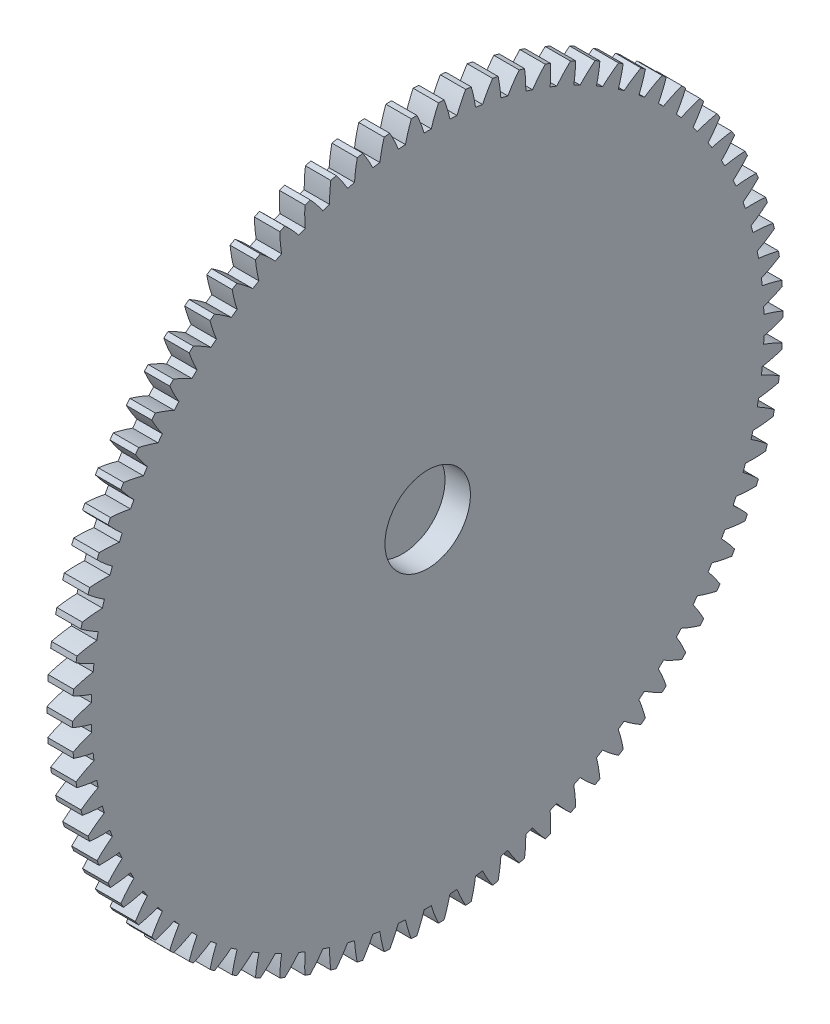
SolidWorks part; units mm, degrees
ref_plane "Plane1" through (0, 0, 0) normal (0, 0, 1) x (1, 0, 0)
ref_plane "Plane2" through (0, 0, 0) normal (0, 1, 0) x (1, 0, 0)
ref_plane "Plane3" through (0, 0, 0) normal (1, 0, 0) x (0, 0, -1)
sketch "HoldingSke" plane through (0, 0, 0) normal (0, 1, 0) x (1, 0, 0)
  line L0 (0, 0) -> (0.1392, -0.9903)
  line L1 (-15, 0) -> (100, 0) construction
  line L2 (0, 0) -> (-2.1039, 2.3779)
  line L3 (0, 0) -> (-11.863, 4.5341)
  line L4 (0, 0) -> (1.2019, 8.552)
  line L5 (0, 0) -> (-46.8476, -17.4728)
  line L6 (0, 0) -> (-2.4869, -1.6779)
  line L7 (-2.1039, 2.3779) -> (8.6586, 51.2059)
  line L8 (-76.2, 54.61) -> (-75.2, 54.61)
  line L9 (-71.009, 38.7566) -> (-53.1078, 45.2721)
  line L10 (-76.2, 71.12) -> (104.1128, 71.12)
  line L11 (0, 0) -> (-3, 0)
  line L12 (-76.2, 101.6) -> (-76.162, 101.6)
  line L13 (24.9733, 27.94) -> (52.9518, 28.4284)
  line L14 (24.9733, 27.94) -> (24.9743, 27.94)
  line L15 (24.9733, 27.94) -> (100.4006, 29.5858)
  line L16 (-63.627, -1) -> (-12.827, -1)
  circle A0 centre (0, 0) radius 3
  circle A1 centre (0, 0) radius 37.5
  circle A2 centre (0, 0) radius 37.5
  circle A3 centre (0, 0) radius 3
  dimension "MHD" = 75
  dimension "Hub_dia" = 75
  dimension "Bore" = 6
  dimension "MBD" = 6
  dimension "Num_teeth" = 82
  dimension "Pitch" = 1
  dimension "Overall_len" = 50
  dimension "Show_teeth" = 82
  dimension "Thickness" = 3
  dimension "OAL" = 50.0001
  dimension "T_dim" = 1
  dimension "Ap" = 20
  dimension "H" = 19.05
  dimension "Pitch_radius" = 180.3128
  dimension "Width" = 3
  dimension "Backlash" = 0.038
  dimension "Addendum_fac" = 1
  dimension "Dedendum_fac" = 1.25
  dimension "Clearance_fac" = 0.25
  dimension "Dedendum_add" = 0.001
  dimension "Module" = 1
sketch "BasProSke" plane through (0, 0, 0) normal (0, 1, 0) x (1, 0, 0)
  line L0 (-10, 0) -> (60, 0) construction
  line L1 (0, 0) -> (0, 42)
  line L2 (0, 0) -> (3, 0)
  line L3 (3, 0) -> (3, 42)
  line L4 (3, 42) -> (0, 42)
  dimension "Thickness" = 3
  dimension "Diameter" = 84
revolve "Base-Revolve" add sketch "BasProSke" angle 360 about L0
sketch "TooCutSke" plane through (0, 0, 0) normal (1, 0, 0) x (0, 0, -1)
  line L1 (0, 0) -> (0, 107) construction
  line L2 (0, 0) -> (-0.8518, 40.9911) construction
  line L3 (0, 0) -> (-3.1403, 81.9272) construction
  line L4 (-0.8518, 40.9911) -> (-1.5702, 40.9636) construction
  arc A0 (0.4198, 39.7468) -> (-0.4198, 39.7468) centre (0, 0) ccw
  arc A1 (1.2904, 42.0056) -> (-1.2904, 42.0056) centre (0, 0) ccw
  circle A2 centre (0, 0) radius 41 construction
  circle A3 centre (0, 0) radius 38.5274 construction
  arc A4 (-0.4198, 39.7468) -> (-1.2904, 42.0056) centre (-16.1163, 34.9947) ccw
  arc A5 (1.2904, 42.0056) -> (0.4198, 39.7468) centre (16.1163, 34.9947) ccw
  dimension "Root_dia" = 79.498
  dimension "Overcut_dia" = 84.0508
  dimension "Pitch_dia" = 82
  dimension "Base_dia" = 77.0548
  dimension "Flank_rad" = 16.4
  dimension "Half_ang" = 2.195
  dimension "Half_CT" = 0.7189
extrude "ToothCut" cut sketch "TooCutSke" along normal through all
fillet "Breaks" [suppressed] radius 0.02 tangent propagation no
fillet "RootFillets" [suppressed] radius 0.251
pattern_circular "TeethCuts" count 82 over 360 about axis through (-10, 0, 0) along (1, 0, 0) of "ToothCut", "RootFillets", "Breaks"
sketch "HubNeaOneSke" plane through (0, 0, 0) normal (-1, 0, 0) x (0, 0, 1)
  circle A0 centre (0, 0) radius 37.5
  dimension "Diameter" = 75
extrude "HubNearOne" [suppressed] add sketch "HubNeaOneSke" along normal blind 47.0001
sketch "HubNeaBotSke" plane through (0, 0, 0) normal (-1, 0, 0) x (0, 0, 1)
  circle A0 centre (0, 0) radius 37.5
  dimension "Diameter" = 75
extrude "HubNearBoth" [suppressed] add sketch "HubNeaBotSke" along normal blind 23.5
ref_plane "FarPln" through (3, 0, 0) normal (1, 0, 0) x (0, 0, -1)
sketch "HubFarSke" plane through (3, 0, 0) normal (1, 0, 0) x (0, 0, -1)
  circle A0 centre (0, 0) radius 37.5
  dimension "Diameter" = 75
extrude "HubFar" [suppressed] add sketch "HubFarSke" along normal blind 23.5
sketch "BorSke" plane through (0, 0, 0) normal (1, 0, 0) x (0, 0, -1)
  circle A0 centre (0, 0) radius 3
  dimension "Diameter" = 6
extrude "Bore" cut sketch "BorSke" along normal mid plane 100.0001
sketch "KeySke" plane through (0, 0, 0) normal (1, 0, 0) x (0, 0, -1)
  line L0 (-1, 0) -> (-1, 4)
  line L1 (-1, 4) -> (1, 4)
  line L2 (1, 4) -> (1, 0)
  line L3 (0, 0) -> (0, 34) construction
  line L4 (-1, 0) -> (1, 0)
  dimension "Offset" = 4
  dimension "Width" = 2
extrude "Keyway" [suppressed] cut sketch "KeySke" along normal mid plane 100.0001
pattern_circular "Keyway2" [suppressed] count 2 every 90 about axis through (-10, 0, 0) along (1, 0, 0) reverse direction yes
sketch "Sketch1" plane through (3, 0, 0) normal (1, 0, 0) x (0, 0, -1)
  circle A0 centre (0, 0) radius 3 construction
  circle A1 centre (0, 0) radius 3
extrude "Boss-Extrude1" add sketch "Sketch1" against normal up to surface (3 mm away) up to face at (0, 0, -3)
sketch "Sketch2" plane through (3, 0, 0) normal (1, 0, 0) x (0, 0, -1)
  line L0 (-1.8, 2.0125) -> (-1.8, -2.0125)
  line L1 (1.8, 2.0125) -> (1.8, -2.0125)
  line L2 (-1.8, 0) -> (1.8, 0) construction
  circle A0 centre (0, 0) radius 2.7
  point P9 (0, 0)
  dimension "D1" = 5.4
  dimension "D2" = 3.6
extrude "Cut-Extrude1" cut sketch "Sketch2" against normal up to surface (3 mm away) contours L0 L2 L1 A0 | L2 L0 A0 L1 region at (3, 1.25, 0) region at (3, -1.25, 0)
sketch "Sketch3" plane through (3, 0, 0) normal (1, 0, 0) x (0, 0, -1)
  circle A0 centre (0, 0) radius 3
  dimension "D1" = 6
extrude "Cut-Extrude2" cut sketch "Sketch3" against normal up to surface (3 mm away)
sketch "Sketch4" plane through (0, 0, 0) normal (-1, 0, 0) x (0, 0, 1)
  circle A0 centre (0, 0) radius 5.05
  dimension "D1" = 10.1
extrude "Cut-Extrude3" cut sketch "Sketch4" against normal through all
sketch "Sketch5" plane through (0, 0, 0) normal (-1, 0, 0) x (0, 0, 1)
  line L1 (6.2989, -3.5812) -> (6.2508, 3.6644)
  line L2 (6.2508, 3.6644) -> (-0.048, 7.2456)
  line L3 (-0.048, 7.2456) -> (-6.2989, 3.5812)
  line L4 (-6.2989, 3.5812) -> (-6.2508, -3.6644)
  line L5 (-6.2508, -3.6644) -> (0.048, -7.2456)
  line L6 (0.048, -7.2456) -> (6.2989, -3.5812)
  circle A0 centre (0, 0) radius 5.05 construction
  circle A1 centre (0, 0) radius 5.05
  circle A2 centre (0, 0) radius 6.275 construction
  dimension "D1" = 12.55
extrude "Boss-Extrude2" add sketch "Sketch5" along normal blind 12.85
sketch "Sketch6" plane through (0, 0, 0) normal (-1, 0, 0) x (0, 0, 1)
  line L12 (0.0557, -8.4003) -> (7.3027, -4.1519)
  line L13 (7.3027, -4.1519) -> (7.247, 4.2484)
  line L14 (7.247, 4.2484) -> (-0.0557, 8.4003)
  line L15 (-0.0557, 8.4003) -> (-7.3027, 4.1519)
  line L16 (-7.3027, 4.1519) -> (-7.247, -4.2484)
  line L17 (-7.247, -4.2484) -> (0.0557, -8.4003)
  line L18 (0.0557, -8.4003) -> (7.3027, -4.1519)
  line L19 (7.3027, -4.1519) -> (7.247, 4.2484)
  line L20 (7.247, 4.2484) -> (-0.0557, 8.4003)
  line L21 (-0.0557, 8.4003) -> (-7.3027, 4.1519)
  line L22 (-7.3027, 4.1519) -> (-7.247, -4.2484)
  line L23 (-7.247, -4.2484) -> (0.0557, -8.4003)
  dimension "D1" = 1
extrude "Boss-Extrude3" add sketch "Sketch6" along normal blind 5.05
equation "' \"Module@HoldingSke\" = 6.35"
equation "' \"Num_teeth@HoldingSke\" = 12"
equation "' \"Ap@HoldingSke\" =  20"
equation "' \"Ap@HoldingSke\" = 20"
equation "' \"Width@HoldingSke\" = 0.5 * 25.4"
equation "' \"Hub_dia@HoldingSke\"= 1 * 25.4"
equation "' \"Hub_dia@HoldingSke\" = 1 * 25.4"
equation "' \"Overall_len@HoldingSke\" = 1.0 * 25.4"
equation "' \"Bore@HoldingSke\" = 0.75 * 25.4"
equation "' \"T_dim@HoldingSke\" = 0.1 * 25.4"
equation "' \"Width@KeySke\" = 0.25 * 25.4"
equation "' \"Show_teeth@HoldingSke\" = 13"
equation "' \"Backlash@HoldingSke\" = 0.009 * 25.4"
equation "' \"Addendum_fac@HoldingSke\" = 1.0"
equation "' \"Dedendum_fac@HoldingSke\" = 1.25"
equation "' \"Dedendum_add@HoldingSke\" = 0.00005 * 25.4"
equation "' \"Clearance_fac@HoldingSke\" = 0.25"
equation "\"Pitch@HoldingSke\" = 1 / \"Module@HoldingSke\""
equation "\"Overcut_dia@TooCutSke\" = (\"Num_teeth@HoldingSke\" + 2 * \"Addendum_fac@HoldingSke\") / \"Pitch@HoldingSke\" + 0.002 * 25.4"
equation "\"Pitch_dia@TooCutSke\" = \"Num_teeth@HoldingSke\" / \"Pitch@HoldingSke\""
equation "\"Base_dia@TooCutSke\" = \"Num_teeth@HoldingSke\" / \"Pitch@HoldingSke\" * cos((\"Ap@HoldingSke\"  * 3.14159265 / 180))"
equation "\"Root_dia@TooCutSke\" = (\"Num_teeth@HoldingSke\" + 2) / \"Pitch@HoldingSke\" - 2 * (\"Addendum_fac@HoldingSke\" + \"Dedendum_fac@HoldingSke\") / \"Pitch@HoldingSke\" - \"Dedendum_add@HoldingSke\" * 2"
equation "\"Half_ang@TooCutSke\" = 180 / \"Num_teeth@HoldingSke\""
equation "\"Half_CT@TooCutSke\" = \"Num_teeth@HoldingSke\" / \"Pitch@HoldingSke\" * sin((3.14159265 / 2 / \"Num_teeth@HoldingSke\")) / 2 - 7 * \"Backlash@HoldingSke\" / 4"
equation "\"Flank_rad@TooCutSke\" = \"Num_teeth@HoldingSke\" / \"Pitch@HoldingSke\" / 5"
equation "\"Radius@RootFillets\" = \"Clearance_fac@HoldingSke\" / \"Pitch@HoldingSke\" + \"Dedendum_add@HoldingSke\""
equation "\"Break_rad@Breaks\" = 0.02 / \"Pitch@HoldingSke\""
equation "\"Thickness@HoldingSke\" = \"Width@HoldingSke\""
equation "\"OAL@HoldingSke\" = \"Thickness@HoldingSke\""
equation "\"MHD@HoldingSke\" = (\"Num_teeth@HoldingSke\" + 2) / \"Pitch@HoldingSke\" - 2 * (\"Addendum_fac@HoldingSke\" + \"Dedendum_fac@HoldingSke\")  / \"Pitch@HoldingSke\" - \"Dedendum_add@HoldingSke\" * 2"
equation "\"MBD@HoldingSke\" = (\"Num_teeth@HoldingSke\" + 2) / \"Pitch@HoldingSke\" - 2 * (\"Addendum_fac@HoldingSke\" + \"Dedendum_fac@HoldingSke\")  / \"Pitch@HoldingSke\" - \"Dedendum_add@HoldingSke\" * 2 - 0.002 * 25.4"
equation "\"MHD@HoldingSke\" = ((sgn( \"MHD@HoldingSke\" - \"Hub_dia@HoldingSke\" )-1)*( \"MHD@HoldingSke\" - \"Hub_dia@HoldingSke\" ))/-2+ \"Hub_dia@HoldingSke\""
equation "\"MBD@HoldingSke\" = ((sgn( \"MBD@HoldingSke\" - \"Bore@HoldingSke\" )-1)*( \"MBD@HoldingSke\" - \"Bore@HoldingSke\" ))/-2+ \"Bore@HoldingSke\""
equation "\"OAL@HoldingSke\" = ((sgn( \"OAL@HoldingSke\" - \"Overall_len@HoldingSke\" )+1)*( \"OAL@HoldingSke\" - \"Overall_len@HoldingSke\" ))/2 + \"Overall_len@HoldingSke\" + 0.000002 * 25.4"
equation "\"Num_teeth@TeethCuts\" = int( \"Show_teeth@HoldingSke\" ) + 1"
equation "\"Num_teeth@TeethCuts\" = ((sgn( \"Num_teeth@TeethCuts\" - \"Num_teeth@HoldingSke\" )-1)*( \"Num_teeth@TeethCuts\" - \"Num_teeth@HoldingSke\" ))/-2+ \"Num_teeth@HoldingSke\""
equation "\"Num_teeth@TeethCuts\" = ((sgn( \"Num_teeth@TeethCuts\" - 2.0)+1)*( \"Num_teeth@TeethCuts\" - 2.0))/2 +2.0"
equation "\"Angle@TeethCuts\" = 360.0 / \"Num_teeth@HoldingSke\""
equation "\"Diameter@BasProSke\" = (\"Num_teeth@HoldingSke\" + 2 * \"Addendum_fac@HoldingSke\") / \"Pitch@HoldingSke\""
equation "\"Thickness@BasProSke\"  = \"Thickness@HoldingSke\""
equation "' \"Fillet_rad@BasProSke\" =  \"Thickness@HoldingSke\" * 0.05"
equation "' \"Fillet_rad@BasProSke\" = \"Thickness@HoldingSke\" * 0.05"
equation "\"MHD@HoldingSke\" = ((sgn( \"MHD@HoldingSke\" - \"Root_dia@TooCutSke\" )-1)*( \"MHD@HoldingSke\" - \"Root_dia@TooCutSke\" ))/-2+ \"Root_dia@TooCutSke\""
equation "\"Diameter@HubNeaOneSke\" = \"MHD@HoldingSke\""
equation "\"Length@HubNearOne\" = \"OAL@HoldingSke\" - \"Thickness@BasProSke\""
equation "\"Diameter@HubNeaBotSke\" = \"MHD@HoldingSke\""
equation "\"Length@HubNearBoth\" = ( \"OAL@HoldingSke\" - \"Thickness@BasProSke\" ) / 2.0"
equation "\"Thickness@FarPln\" = \"Thickness@BasProSke\""
equation "\"Diameter@HubFarSke\" = \"MHD@HoldingSke\""
equation "\"Length@HubFar\" = ( \"OAL@HoldingSke\" - \"Thickness@BasProSke\" ) / 2.0"
equation "\"Diameter@BorSke\" = \"MBD@HoldingSke\""
equation "\"D1@Bore\" = \"OAL@HoldingSke\" * 2.0"
equation "\"D1@Keyway\" = \"OAL@HoldingSke\" * 2.0"
equation "\"Offset@KeySke\" = \"T_dim@HoldingSke\" + \"MBD@HoldingSke\" / 2.0"
